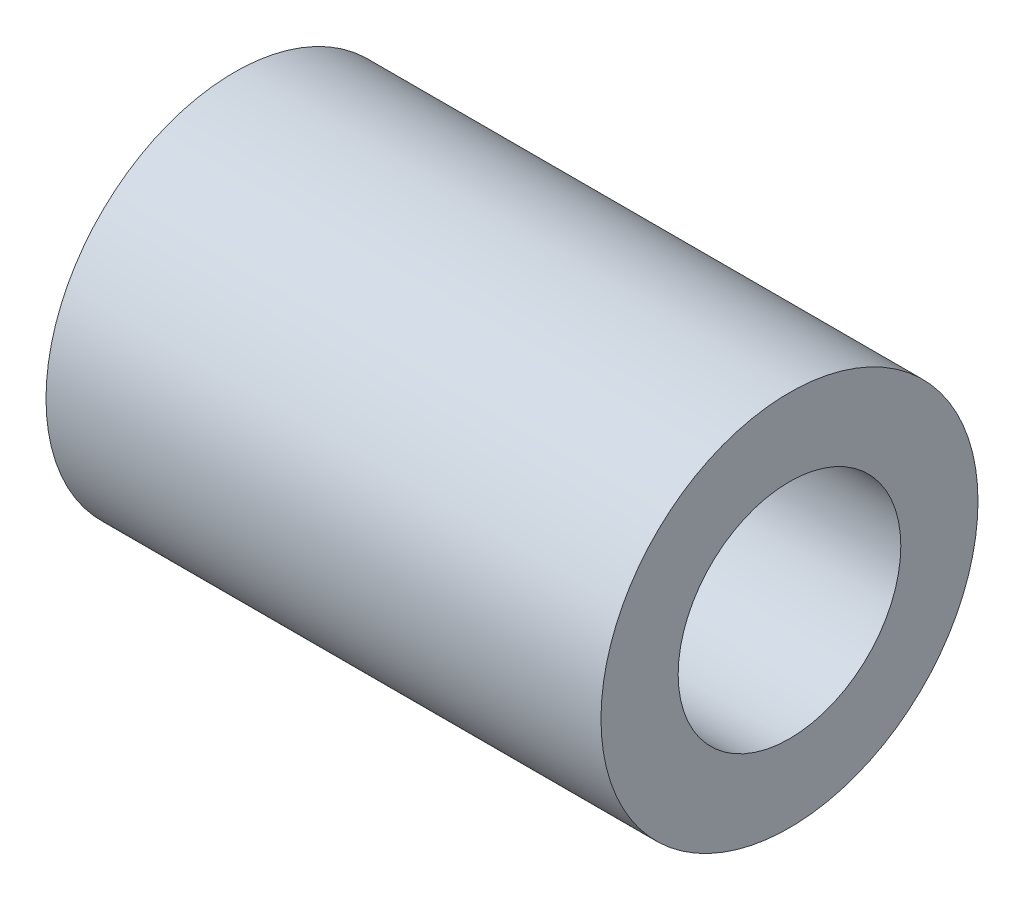
SolidWorks part; units mm, degrees
material "PLA"
ref_plane "Front Plane" through (0, 0, 0) normal (0, 0, 1) x (1, 0, 0)
ref_plane "Top Plane" through (0, 0, 0) normal (0, 1, 0) x (1, 0, 0)
ref_plane "Right Plane" through (0, 0, 0) normal (1, 0, 0) x (0, 0, -1)
sketch "Sketch1" plane through (0, 0, 0) normal (1, 0, 0) x (0, 0, -1)
  circle A0 centre (0, 0) radius 3.175
  circle A1 centre (0, 0) radius 5.08
  circle A2 centre (0, 0) radius 3
  dimension "D1" = 6.35
  dimension "D2" = 10.16
  dimension "D3" = 6
extrude "Boss-Extrude1" add sketch "Sketch1" against normal blind 3.175 contours A1 A0 region at (0, 0, 4.9363)
extrude "Boss-Extrude2" add sketch "Sketch1<3>" along normal blind 11.7805 contours A0 A2 | A1 A0 region at (0, 0, 3.0852) region at (0, 0, 4.9363)
sketch "Sketch1<3>" plane through (0, 0, 0) normal (1, 0, 0) x (0, 0, -1) same geometry as "Sketch1"
